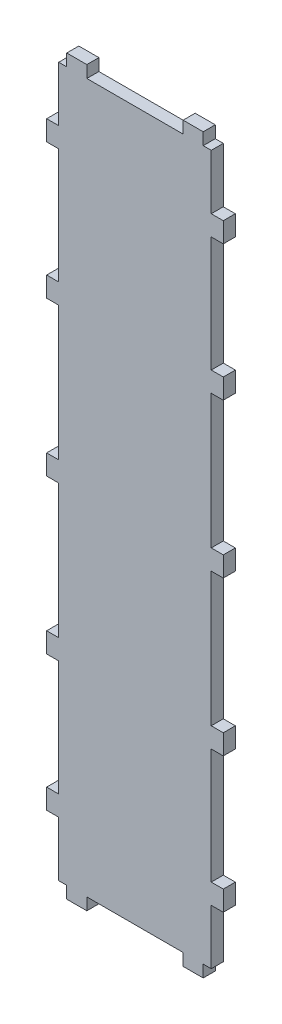
SolidWorks part; units mm, degrees
ref_plane "Front Plane" through (0, 0, 0) normal (0, 0, 1) x (1, 0, 0)
ref_plane "Top Plane" through (0, 0, 0) normal (0, 1, 0) x (1, 0, 0)
ref_plane "Right Plane" through (0, 0, 0) normal (1, 0, 0) x (0, 0, -1)
sketch "Sketch1" plane through (0, 0, 0) normal (0, 0, 1) x (1, 0, 0)
  line L0 (88, -184.1956) -> (-175.75, -184.1956) construction
  line L1 (-175.75, -184.1956) -> (-175.75, 910.041) construction
  line L2 (88, 910.041) -> (-175.75, 910.041) construction
  line L3 (88, -184.1956) -> (88, 910.041) construction
  line L4 (88, -184.1956) -> (-175.75, -184.1956)
  line L5 (-175.75, -184.1956) -> (-175.75, 910.041)
  line L6 (88, 910.041) -> (-175.75, 910.041)
  line L7 (88, -184.1956) -> (88, 910.041)
extrude "Boss-Extrude1" add sketch "Sketch1" along normal blind 18
sketch "Sketch2" plane through (0, 0, 0) normal (0, 0, -1) x (-1, 0, 0)
  line L0 (175.75, 910.041) -> (175.75, -184.1956) construction
  line L5 (175.75, 147.9227) -> (157.75, 147.9227)
  line L6 (175.75, 147.9227) -> (175.75, 347.9227)
  line L7 (157.75, -166.1956) -> (-750.1515, -166.1956) construction
  line L12 (-88, -184.1956) -> (175.75, -184.1956) construction
  line L13 (175.75, -184.1956) -> (145.75, -184.1956)
  line L14 (175.75, -184.1956) -> (175.75, -84.1956)
  line L15 (157.75, -166.1956) -> (145.75, -166.1956)
  line L16 (145.75, -184.1956) -> (145.75, -166.1956)
  line L17 (115.75, -166.1956) -> (43.875, -166.1956)
  line L18 (115.75, -166.1956) -> (115.75, -184.1956)
  line L19 (115.75, -184.1956) -> (-28, -184.1956)
  line L28 (175.75, 362.9227) -> (-88, 362.9227) construction
  line L42 (157.75, 910.041) -> (157.75, -184.1956) construction
  line L44 (157.75, -166.1956) -> (157.75, -84.1956)
  line L45 (157.75, -84.1956) -> (175.75, -84.1956)
  line L47 (175.75, 910.041) -> (175.75, -184.1956) construction
  line L48 (157.75, -54.1956) -> (175.75, -54.1956)
  line L49 (157.75, -54.1956) -> (157.75, 117.9227)
  line L50 (157.75, 117.9227) -> (175.75, 117.9227)
  line L51 (175.75, -54.1956) -> (175.75, 117.9227)
  line L76 (175.75, 347.9227) -> (157.75, 347.9227)
  line L77 (157.75, 147.9227) -> (157.75, 347.9227)
  line L90 (-88, -184.1956) -> (-88, 910.041) construction
  line L91 (43.875, 910.041) -> (43.875, -184.1956) construction
  line L92 (-88, 910.041) -> (175.75, 910.041) construction
  line L93 (-70, 147.9227) -> (-70, 347.9227)
  line L94 (-88, 347.9227) -> (-70, 347.9227)
  line L95 (-88, -54.1956) -> (-88, 117.9227)
  line L96 (-70, 117.9227) -> (-88, 117.9227)
  line L97 (-70, -54.1956) -> (-70, 117.9227)
  line L98 (-70, -54.1956) -> (-88, -54.1956)
  line L99 (-70, -84.1956) -> (-88, -84.1956)
  line L100 (-70, -166.1956) -> (-70, -84.1956)
  line L101 (-28, -166.1956) -> (-28, -184.1956)
  line L102 (-28, -166.1956) -> (43.875, -166.1956)
  line L103 (-58, -184.1956) -> (-58, -166.1956)
  line L104 (-70, -166.1956) -> (-58, -166.1956)
  line L105 (-88, -184.1956) -> (-88, -84.1956)
  line L106 (-88, -184.1956) -> (-58, -184.1956)
  line L107 (-88, 147.9227) -> (-88, 347.9227)
  line L108 (-88, 147.9227) -> (-70, 147.9227)
  line L109 (-88, 577.9227) -> (-70, 577.9227)
  line L110 (-88, 577.9227) -> (-88, 377.9227)
  line L111 (-88, 910.041) -> (-58, 910.041)
  line L112 (-88, 910.041) -> (-88, 810.041)
  line L113 (-70, 892.041) -> (-58, 892.041)
  line L114 (-58, 910.041) -> (-58, 892.041)
  line L115 (-28, 892.041) -> (43.875, 892.041)
  line L116 (-28, 892.041) -> (-28, 910.041)
  line L117 (-70, 892.041) -> (-70, 810.041)
  line L118 (-70, 810.041) -> (-88, 810.041)
  line L119 (-70, 780.041) -> (-88, 780.041)
  line L120 (-70, 780.041) -> (-70, 607.9227)
  line L121 (-70, 607.9227) -> (-88, 607.9227)
  line L122 (-88, 780.041) -> (-88, 607.9227)
  line L123 (-88, 377.9227) -> (-70, 377.9227)
  line L124 (-70, 577.9227) -> (-70, 377.9227)
  line L125 (157.75, 577.9227) -> (157.75, 377.9227)
  line L126 (175.75, 377.9227) -> (157.75, 377.9227)
  line L127 (175.75, 780.041) -> (175.75, 607.9227)
  line L128 (157.75, 607.9227) -> (175.75, 607.9227)
  line L129 (157.75, 780.041) -> (157.75, 607.9227)
  line L130 (157.75, 780.041) -> (175.75, 780.041)
  line L131 (157.75, 810.041) -> (175.75, 810.041)
  line L132 (157.75, 892.041) -> (157.75, 810.041)
  line L134 (115.75, 910.041) -> (-28, 910.041)
  line L135 (115.75, 892.041) -> (115.75, 910.041)
  line L136 (115.75, 892.041) -> (43.875, 892.041)
  line L137 (145.75, 910.041) -> (145.75, 892.041)
  line L138 (157.75, 892.041) -> (145.75, 892.041)
  line L139 (175.75, 910.041) -> (175.75, 810.041)
  line L140 (175.75, 910.041) -> (145.75, 910.041)
  line L141 (175.75, 577.9227) -> (175.75, 377.9227)
  line L142 (175.75, 577.9227) -> (157.75, 577.9227)
  point P3 (79.8125, -166.1956)
  point P39 (7.9375, -166.1956)
  point P88 (7.9375, 892.041)
  point P89 (79.8125, 892.041)
  dimension "D1" = 30
  dimension "D2" = 30
  dimension "D3" = 30
  dimension "D4" = 100
  dimension "D5" = 30
  dimension "D6" = 15
  dimension "D7" = 200
extrude "Cut-Extrude2" cut sketch "Sketch2" against normal blind 18
equation "\"osbthickness\"=18"
equation "\"D1@Boss-Extrude1\"=\"osbthickness\""
equation "\"finger\"=30"
equation "\"D1@Sketch2\"=\"finger\""
equation "\"fingerclearance\"=100"
equation "\"D4@Sketch2\"=\"fingerclearance\""
equation "\"D3@Sketch2\"=\"finger\""
equation "\"D5@Sketch2\"=\"finger\""
